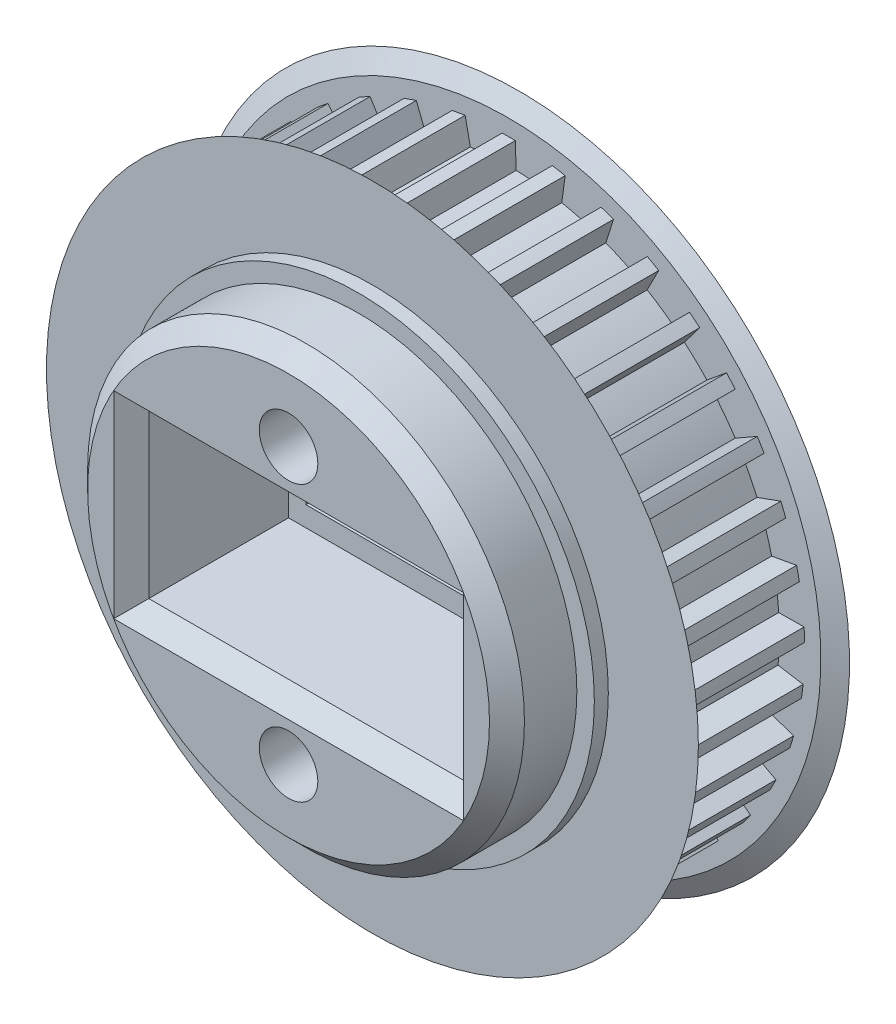
SolidWorks part; units mm, degrees
material "ABS"
ref_plane "Alzado" through (0, 0, 0) normal (0, 0, 1) x (1, 0, 0)
ref_plane "Planta" through (0, 0, 0) normal (0, 1, 0) x (1, 0, 0)
ref_plane "Vista lateral" through (0, 0, 0) normal (1, 0, 0) x (0, 0, -1)
sketch "Croquis1" plane through (0, 0, 0) normal (0, 0, 1) x (1, 0, 0)
  line L0 (0, 0) -> (0, 14.5885) construction
  line L1 (-0.375, 16.9338) -> (-0.425, 15.4822)
  line L2 (0.375, 16.9338) -> (0.425, 15.4822)
  line L3 (3.2314, 16.6269) -> (3.0354, 15.1876)
  line L4 (2.4922, 16.7536) -> (2.1976, 15.3313)
  line L5 (5.9949, 15.8416) -> (5.5584, 14.4562)
  line L6 (5.2878, 16.0915) -> (4.757, 14.7394)
  line L7 (8.5859, 14.6006) -> (7.9216, 13.3089)
  line L8 (7.9312, 14.9664) -> (7.1795, 13.7234)
  line L9 (10.9299, 12.9396) -> (10.0569, 11.7787)
  line L10 (10.3464, 13.4107) -> (9.3955, 12.3127)
  line L11 (12.9595, 10.9063) -> (11.9028, 9.9096)
  line L12 (12.464, 11.4693) -> (11.3412, 10.5477)
  line L13 (14.6163, 8.5592) -> (13.4063, 7.7555)
  line L14 (14.223, 9.1979) -> (12.9607, 8.4793)
  line L15 (15.8525, 5.9659) -> (14.5242, 5.3783)
  line L16 (15.5729, 6.6619) -> (14.2073, 6.167)
  line L17 (16.6328, 3.201) -> (15.2242, 2.8463)
  line L18 (16.4748, 3.9342) -> (15.0451, 3.6772)
  line L19 (16.9345, 0.344) -> (15.4863, 0.2325)
  line L20 (16.9027, 1.0934) -> (15.4502, 1.0817)
  line L21 (16.7491, -2.5229) -> (15.3028, -2.3881)
  line L22 (16.8443, -1.7789) -> (15.4107, -1.545)
  line L23 (16.0818, -5.3172) -> (14.6791, -4.9399)
  line L24 (16.3014, -4.6001) -> (14.928, -4.1272)
  line L25 (14.9518, -7.9585) -> (13.6331, -7.3496)
  line L26 (15.2895, -7.2888) -> (14.0158, -6.5906)
  line L27 (13.3918, -10.3709) -> (12.1949, -9.5479)
  line L28 (13.8377, -9.7679) -> (12.7003, -8.8645)
  line L29 (11.4465, -12.485) -> (10.4059, -11.4715)
  line L30 (11.9879, -11.966) -> (11.0195, -10.8834)
  line L31 (9.1718, -14.2398) -> (8.3175, -13.0651)
  line L32 (9.7932, -13.8199) -> (9.0217, -12.5891)
  line L33 (6.6334, -15.5851) -> (5.9899, -14.2828)
  line L34 (7.3168, -15.2761) -> (6.7644, -13.9327)
  line L35 (3.9041, -16.4819) -> (3.4899, -15.0897)
  line L36 (4.6299, -16.2929) -> (4.3125, -14.8755)
  line L37 (1.0624, -16.9046) -> (0.8895, -15.4624)
  line L38 (1.8097, -16.841) -> (1.7364, -15.3903)
  line L39 (-1.8097, -16.841) -> (-1.7364, -15.3903)
  line L40 (-1.0624, -16.9046) -> (-0.8895, -15.4624)
  line L41 (-4.6299, -16.2929) -> (-4.3125, -14.8755)
  line L42 (-3.9041, -16.4819) -> (-3.4899, -15.0897)
  line L43 (-7.3168, -15.2761) -> (-6.7644, -13.9327)
  line L44 (-6.6334, -15.5851) -> (-5.9899, -14.2828)
  line L45 (-9.7932, -13.8199) -> (-9.0217, -12.5891)
  line L46 (-9.1718, -14.2398) -> (-8.3175, -13.0651)
  line L47 (-11.9879, -11.966) -> (-11.0195, -10.8834)
  line L48 (-11.4465, -12.485) -> (-10.4059, -11.4715)
  line L49 (-13.8377, -9.7679) -> (-12.7003, -8.8645)
  line L50 (-13.3918, -10.3709) -> (-12.1949, -9.5479)
  line L51 (-15.2895, -7.2888) -> (-14.0158, -6.5906)
  line L52 (-14.9518, -7.9585) -> (-13.6331, -7.3496)
  line L53 (-16.3014, -4.6001) -> (-14.928, -4.1272)
  line L54 (-16.0818, -5.3172) -> (-14.6791, -4.9399)
  line L55 (-16.8443, -1.7789) -> (-15.4107, -1.545)
  line L56 (-16.7491, -2.5229) -> (-15.3028, -2.3881)
  line L57 (-16.9027, 1.0934) -> (-15.4502, 1.0817)
  line L58 (-16.9345, 0.344) -> (-15.4863, 0.2325)
  line L59 (-16.4748, 3.9342) -> (-15.0451, 3.6772)
  line L60 (-16.6328, 3.201) -> (-15.2242, 2.8463)
  line L61 (-15.5729, 6.6619) -> (-14.2073, 6.167)
  line L62 (-15.8525, 5.9659) -> (-14.5242, 5.3783)
  line L63 (-14.223, 9.1979) -> (-12.9607, 8.4793)
  line L64 (-14.6163, 8.5592) -> (-13.4063, 7.7555)
  line L65 (-12.464, 11.4693) -> (-11.3412, 10.5477)
  line L66 (-12.9595, 10.9063) -> (-11.9028, 9.9096)
  line L67 (-10.3464, 13.4107) -> (-9.3955, 12.3127)
  line L68 (-10.9299, 12.9396) -> (-10.0569, 11.7787)
  line L69 (-7.9312, 14.9664) -> (-7.1795, 13.7234)
  line L70 (-8.5859, 14.6006) -> (-7.9216, 13.3089)
  line L71 (-5.2878, 16.0915) -> (-4.757, 14.7394)
  line L72 (-5.9949, 15.8416) -> (-5.5584, 14.4562)
  line L73 (-2.4922, 16.7536) -> (-2.1976, 15.3313)
  line L74 (-3.2314, 16.6269) -> (-3.0354, 15.1876)
  line L75 (-3.2314, 16.6269) -> (-2.4922, 16.7536)
  arc A0 (-12.464, 11.4693) -> (-12.9595, 10.9063) centre (0, 0) ccw
  arc A1 (2.1976, 15.3313) -> (0.425, 15.4822) centre (0, 0) ccw
  arc A2 (-14.223, 9.1979) -> (-14.6163, 8.5592) centre (0, 0) ccw
  arc A3 (-15.5729, 6.6619) -> (-15.8525, 5.9659) centre (0, 0) ccw
  arc A4 (-16.4748, 3.9342) -> (-16.6328, 3.201) centre (0, 0) ccw
  arc A5 (-16.9027, 1.0934) -> (-16.9345, 0.344) centre (0, 0) ccw
  arc A6 (-16.8443, -1.7789) -> (-16.7491, -2.5229) centre (0, 0) ccw
  arc A7 (-16.3014, -4.6001) -> (-16.0818, -5.3172) centre (0, 0) ccw
  arc A8 (-15.2895, -7.2888) -> (-14.9518, -7.9585) centre (0, 0) ccw
  arc A9 (-13.8377, -9.7679) -> (-13.3918, -10.3709) centre (0, 0) ccw
  arc A10 (-11.9879, -11.966) -> (-11.4465, -12.485) centre (0, 0) ccw
  arc A11 (3.2314, 16.6269) -> (2.4922, 16.7536) centre (0, 0) ccw
  arc A12 (0.375, 16.9338) -> (-0.375, 16.9338) centre (0, 0) ccw
  arc A13 (-7.9312, 14.9664) -> (-8.5859, 14.6006) centre (0, 0) ccw
  arc A14 (-10.3464, 13.4107) -> (-10.9299, 12.9396) centre (0, 0) ccw
  arc A15 (-5.2878, 16.0915) -> (-5.9949, 15.8416) centre (0, 0) ccw
  arc A16 (5.9949, 15.8416) -> (5.2878, 16.0915) centre (0, 0) ccw
  arc A17 (8.5859, 14.6006) -> (7.9312, 14.9664) centre (0, 0) ccw
  arc A18 (10.9299, 12.9396) -> (10.3464, 13.4107) centre (0, 0) ccw
  arc A19 (12.9595, 10.9063) -> (12.464, 11.4693) centre (0, 0) ccw
  arc A20 (14.6163, 8.5592) -> (14.223, 9.1979) centre (0, 0) ccw
  arc A21 (15.8525, 5.9659) -> (15.5729, 6.6619) centre (0, 0) ccw
  arc A22 (16.6328, 3.201) -> (16.4748, 3.9342) centre (0, 0) ccw
  arc A23 (16.9345, 0.344) -> (16.9027, 1.0934) centre (0, 0) ccw
  arc A24 (16.7491, -2.5229) -> (16.8443, -1.7789) centre (0, 0) ccw
  arc A25 (16.0818, -5.3172) -> (16.3014, -4.6001) centre (0, 0) ccw
  arc A26 (9.1718, -14.2398) -> (9.7932, -13.8199) centre (0, 0) ccw
  arc A27 (6.6334, -15.5851) -> (7.3168, -15.2761) centre (0, 0) ccw
  arc A28 (3.9041, -16.4819) -> (4.6299, -16.2929) centre (0, 0) ccw
  arc A29 (-1.8097, -16.841) -> (-1.0624, -16.9046) centre (0, 0) ccw
  arc A30 (-4.6299, -16.2929) -> (-3.9041, -16.4819) centre (0, 0) ccw
  arc A31 (-7.3168, -15.2761) -> (-6.6334, -15.5851) centre (0, 0) ccw
  arc A32 (-9.7932, -13.8199) -> (-9.1718, -14.2398) centre (0, 0) ccw
  arc A33 (11.4465, -12.485) -> (11.9879, -11.966) centre (0, 0) ccw
  arc A34 (13.3918, -10.3709) -> (13.8377, -9.7679) centre (0, 0) ccw
  arc A35 (14.9518, -7.9585) -> (15.2895, -7.2888) centre (0, 0) ccw
  arc A36 (4.757, 14.7394) -> (3.0354, 15.1876) centre (0, 0) ccw
  arc A37 (7.1795, 13.7234) -> (5.5584, 14.4562) centre (0, 0) ccw
  arc A38 (-5.5584, 14.4562) -> (-7.1795, 13.7234) centre (0, 0) ccw
  arc A39 (-0.425, 15.4822) -> (-2.1976, 15.3313) centre (0, 0) ccw
  arc A40 (-7.9216, 13.3089) -> (-9.3955, 12.3127) centre (0, 0) ccw
  arc A41 (-10.0569, 11.7787) -> (-11.3412, 10.5477) centre (0, 0) ccw
  arc A42 (-11.9028, 9.9096) -> (-12.9607, 8.4793) centre (0, 0) ccw
  arc A43 (9.3955, 12.3127) -> (7.9216, 13.3089) centre (0, 0) ccw
  arc A44 (11.3412, 10.5477) -> (10.0569, 11.7787) centre (0, 0) ccw
  arc A45 (12.9607, 8.4793) -> (11.9028, 9.9096) centre (0, 0) ccw
  arc A46 (14.2073, 6.167) -> (13.4063, 7.7555) centre (0, 0) ccw
  arc A47 (15.0451, 3.6772) -> (14.5242, 5.3783) centre (0, 0) ccw
  arc A48 (15.4502, 1.0817) -> (15.2242, 2.8463) centre (0, 0) ccw
  arc A49 (15.4107, -1.545) -> (15.4863, 0.2325) centre (0, 0) ccw
  arc A50 (14.928, -4.1272) -> (15.3028, -2.3881) centre (0, 0) ccw
  arc A51 (14.0158, -6.5906) -> (14.6791, -4.9399) centre (0, 0) ccw
  arc A52 (12.7003, -8.8645) -> (13.6331, -7.3496) centre (0, 0) ccw
  arc A53 (11.0195, -10.8834) -> (12.1949, -9.5479) centre (0, 0) ccw
  arc A54 (9.0217, -12.5891) -> (10.4059, -11.4715) centre (0, 0) ccw
  arc A55 (6.7644, -13.9327) -> (8.3175, -13.0651) centre (0, 0) ccw
  arc A56 (4.3125, -14.8755) -> (5.9899, -14.2828) centre (0, 0) ccw
  arc A57 (1.7364, -15.3903) -> (3.4899, -15.0897) centre (0, 0) ccw
  arc A58 (-0.8895, -15.4624) -> (0.8895, -15.4624) centre (0, 0) ccw
  arc A59 (-3.4899, -15.0897) -> (-1.7364, -15.3903) centre (0, 0) ccw
  arc A60 (-5.9899, -14.2828) -> (-4.3125, -14.8755) centre (0, 0) ccw
  arc A61 (-8.3175, -13.0651) -> (-6.7644, -13.9327) centre (0, 0) ccw
  arc A62 (-10.4059, -11.4715) -> (-9.0217, -12.5891) centre (0, 0) ccw
  arc A63 (-12.1949, -9.5479) -> (-11.0195, -10.8834) centre (0, 0) ccw
  arc A64 (-13.6331, -7.3496) -> (-12.7003, -8.8645) centre (0, 0) ccw
  arc A65 (-14.6791, -4.9399) -> (-14.0158, -6.5906) centre (0, 0) ccw
  arc A66 (-15.3028, -2.3881) -> (-14.928, -4.1272) centre (0, 0) ccw
  arc A67 (-15.4863, 0.2325) -> (-15.4107, -1.545) centre (0, 0) ccw
  arc A68 (-15.2242, 2.8463) -> (-15.4502, 1.0817) centre (0, 0) ccw
  arc A69 (-14.5242, 5.3783) -> (-15.0451, 3.6772) centre (0, 0) ccw
  arc A70 (-13.4063, 7.7555) -> (-14.2073, 6.167) centre (0, 0) ccw
  arc A71 (1.0624, -16.9046) -> (1.8097, -16.841) centre (0, 0) ccw
  circle A72 centre (0, 0) radius 2
  arc A73 (-3.0354, 15.1876) -> (-4.757, 14.7394) centre (0, 0) ccw
  point P151 (0, 0)
  dimension "D1" = 1.45
  dimension "D6" = 4
  dimension "D2" = 0.85
  dimension "D3" = 0.75
  dimension "D5" = 1.78
  dimension "D4" = 37
extrude "Saliente-Extruir1" add sketch "Croquis1" along normal blind 7.2
sketch "Croquis2" plane through (0, 0, 7.2) normal (0, 0, 1) x (1, 0, 0)
  circle A0 centre (0, 0) radius 19
  circle A1 centre (0, 0) radius 2
  circle A2 centre (0, 0) radius 2 construction
  dimension "D1" = 38
extrude "Saliente-Extruir2" add sketch "Croquis2" along normal blind 0.6
sketch "Croquis3" plane through (0, 0, 7.8) normal (0, 0, 1) x (1, 0, 0)
  circle A0 centre (0, 0) radius 2
  circle A1 centre (0, 0) radius 12.5
  circle A3 centre (0, 0) radius 2 construction
  dimension "D1" = 25
sketch "Croquis4" plane through (0, 0, 0) normal (0, 0, -1) x (-1, 0, 0)
  circle A0 centre (0, 0) radius 2
  circle A1 centre (0, 0) radius 12.45
  circle A2 centre (0, 0) radius 2 construction
  dimension "D1" = 24.9
extrude "Saliente-Extruir4" add sketch "Croquis4" along normal blind 5.8
sketch "Croquis6" plane through (0, 0, 0) normal (0, 0, -1) x (-1, 0, 0)
  circle A0 centre (0, 0) radius 19.25
  circle A1 centre (0, 0) radius 2
  circle A2 centre (0, 0) radius 2 construction
  dimension "D1" = 38.5
extrude "Saliente-Extruir6" add sketch "Croquis6" along normal blind 0.6
sketch "Croquis5" plane through (0, 0, -0.6) normal (0, 0, -1) x (-1, 0, 0)
  circle A0 centre (0, 0) radius 2
  circle A1 centre (0, 0) radius 13.5
  circle A2 centre (0, 0) radius 2 construction
  dimension "D1" = 27
extrude "Saliente-Extruir5" add sketch "Croquis5" along normal blind 0.6
chamfer "Chaflán2" distance 0.8 angle 60 2 edges at (-19.25, 0, 0) (19, 0, 7.2)
extrude "Saliente-Extruir7" add sketch "Croquis3" along normal blind 4.8
chamfer "Chaflán4" distance 1 angle 45 2 edges at (-12.45, 0, -5.8) (12.5, 0, 12.6)
sketch "Croquis7" plane through (0, 0, 7.8) normal (0, 0, 1) x (1, 0, 0)
  circle A0 centre (0, 0) radius 2
  circle A1 centre (0, 0) radius 13.5
  circle A2 centre (0, 0) radius 2 construction
  dimension "D1" = 27
extrude "Saliente-Extruir8" add sketch "Croquis7" along normal blind 0.8
sketch "Croquis8" plane through (0, 0, 0) normal (0, 0, 1) x (1, 0, 0)
  line L0 (0, 0) -> (6.706, 0) construction
  line L1 (-8, 3.5) -> (8, 3.5)
  line L2 (-8, 3.5) -> (-8, -3.5)
  line L3 (-8, -3.5) -> (8, -3.5)
  line L4 (8, 3.5) -> (8, -3.5)
  line L5 (-8, 3.5) -> (8, -3.5) construction
  line L6 (-8, -3.5) -> (8, 3.5) construction
  circle A0 centre (0, 7.8756) radius 1.675
  circle A1 centre (0, -7.8756) radius 1.675
  point P0 (0, 0)
  dimension "D1" = 3.35
  dimension "D2" = 7
  dimension "D3" = 16
extrude "Cortar-Extruir1" cut sketch "Croquis8" against normal through all both and the other way through all
sketch "Croquis9" plane through (0, 0, -5.8) normal (0, 0, -1) x (-1, 0, 0)
  line L1 (2.3383, 3.8256) -> (4.6765, 7.8756)
  line L2 (4.6765, 7.8756) -> (2.3383, 11.9256)
  line L3 (2.3383, 11.9256) -> (-2.3383, 11.9256)
  line L4 (-2.3383, 11.9256) -> (-4.6765, 7.8756)
  line L5 (-4.6765, 7.8756) -> (-2.3383, 3.8256)
  line L6 (-2.3383, 3.8256) -> (2.3383, 3.8256)
  line L7 (2.3383, -11.9256) -> (4.6765, -7.8756)
  line L8 (4.6765, -7.8756) -> (2.3383, -3.8256)
  line L9 (2.3383, -3.8256) -> (-2.3383, -3.8256)
  line L10 (-2.3383, -3.8256) -> (-4.6765, -7.8756)
  line L11 (-4.6765, -7.8756) -> (-2.3383, -11.9256)
  line L12 (-2.3383, -11.9256) -> (2.3383, -11.9256)
  circle A0 centre (0, 7.8756) radius 4.05 construction
  circle A1 centre (0, -7.8756) radius 4.05 construction
  dimension "D1" = 8.1
extrude "Cortar-Extruir2" cut sketch "Croquis9" against normal blind 4
fillet "Redondeo1" radius 2.5 12 edges at (3.5074, -9.9006, -1.8) (3.5074, -5.8506, -1.8) (0, -3.8256, -1.8) (-3.5074, -5.8506, -1.8) (0, -11.9256, -1.8) (-3.5074, -9.9006, -1.8) (-3.5074, 5.8506, -1.8) (-3.5074, 9.9006, -1.8) (0, 11.9256, -1.8) (3.5074, 9.9006, -1.8) (3.5074, 5.8506, -1.8) (0, 3.8256, -1.8)
sketch "Croquis10" plane through (0, 0, 12.6) normal (0, 0, 1) x (1, 0, 0)
  line L1 (9, 4.65) -> (-9, 4.65)
  line L2 (9, 4.65) -> (9, -4.65)
  line L3 (9, -4.65) -> (-9, -4.65)
  line L4 (-9, 4.65) -> (-9, -4.65)
  line L5 (9, 4.65) -> (-9, -4.65) construction
  line L6 (9, -4.65) -> (-9, 4.65) construction
  point P0 (0, 0)
  dimension "D1" = 9.3
  dimension "D2" = 18
extrude "Cortar-Extruir3" cut sketch "Croquis10" against normal blind 9
chamfer "Chaflán5" distance 1 angle 45 8 edges at (-8, 0, -5.8) (0, 3.5, -5.8) (8, 0, -5.8) (0, -3.5, -5.8) (9, 0, 12.6) (0, 4.65, 12.6) (-9, 0, 12.6) (0, -4.65, 12.6)
